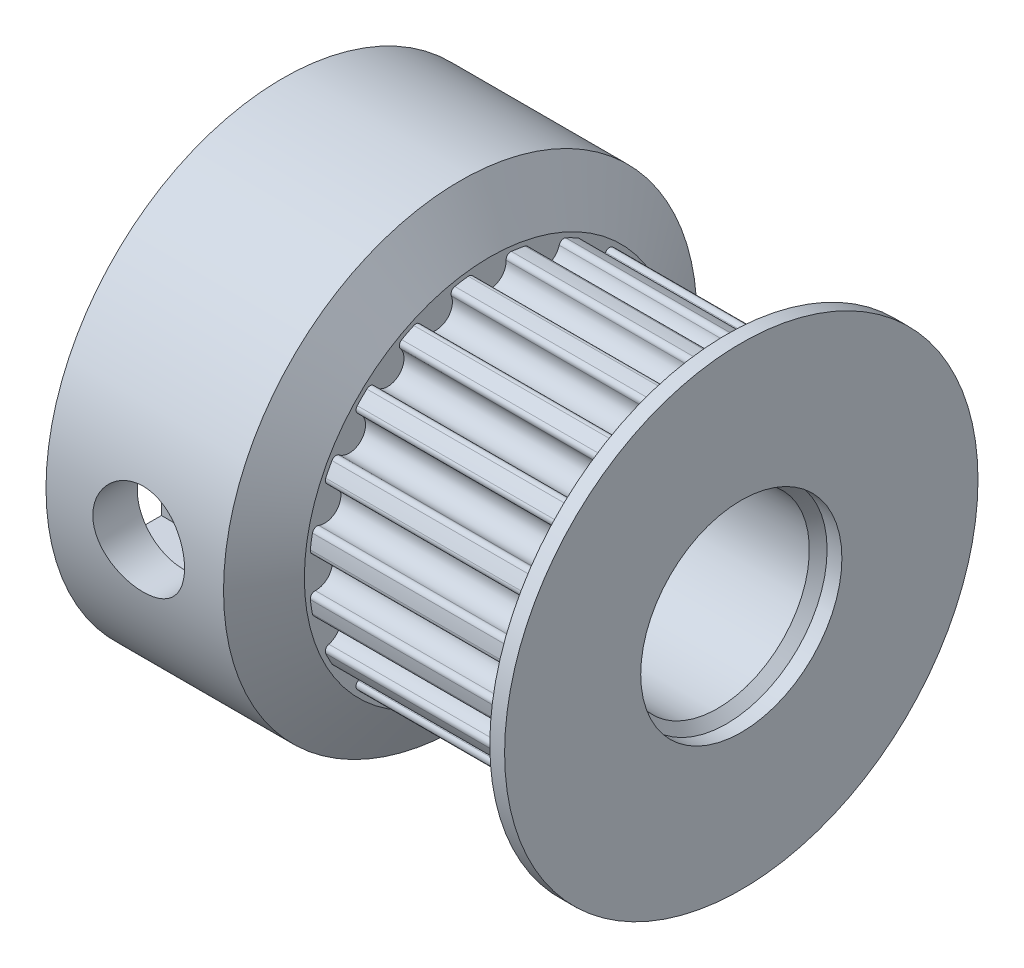
SolidWorks part; units mm, degrees
note: '?' marks a value the reader was unsure of.
other "Main_Body" parameters "D16"=0.5
material "6061-O (SS)"
ref_plane "Сверху" through (0, 0, 0) normal (0, 0, 1) x (1, 0, 0)
ref_plane "Справа" through (0, 0, 0) normal (0, 1, 0) x (1, 0, 0)
ref_plane "Спереди" through (0, 0, 0) normal (1, 0, 0) x (0, 0, -1)
sketch "Эскиз1" plane through (0, 0, 0) normal (0, 0, 1) x (1, 0, 0)
  line L0 (0, 0) -> (0, 7.2132)
  line L1 (0, 7.2132) -> (0, 8)
  line L2 (0, 8) -> (7, 8)
  line L3 (7, 8) -> (7, 7.2132)
  line L4 (7, 6.11) -> (14, 6.11)
  line L5 (14, 6.11) -> (14, 7.2132)
  line L6 (14, 8) -> (15, 8)
  line L7 (15, 0) -> (15, 8)
  line L11 (0, 0) -> (15, 0)
  line L12 (7, 7.2132) -> (7, 6.11)
  line L13 (14, 7.2132) -> (14, 8)
  dimension "D6" = 6.11
  dimension "D7" = 7
  dimension "D8" = 7
  dimension "D10" = 15
  dimension "D11" = 8
revolve "Body" add sketch "Эскиз1" angle 360 about L11
sketch "Эскиз2" plane through (15, 0, 0) normal (1, 0, 0) x (0, 0, -1)
  circle A0 centre (0, 0) radius 3.1
  dimension "D1" = 6.2
extrude "Bore" cut sketch "Эскиз2" against normal through all
sketch "Эскиз3" plane through (7, 0, 0) normal (1, 0, 0) x (0, 0, -1)
  line L0 (0, 0) -> (9.7637, 0) construction
  circle A0 centre (5.5827, -1.8139) radius 0.55
  circle A1 centre (0, 0) radius 6.42 construction
  circle A2 centre (4.7489, -3.4503) radius 0.55
  circle A3 centre (3.4503, -4.7489) radius 0.55
  circle A4 centre (1.8139, -5.5827) radius 0.55
  circle A5 centre (0, -5.87) radius 0.55
  circle A6 centre (5.87, 0) radius 0.55
  circle A7 centre (-1.8139, -5.5827) radius 0.55
  circle A8 centre (-3.4503, -4.7489) radius 0.55
  circle A9 centre (-4.7489, -3.4503) radius 0.55
  circle A10 centre (-5.5827, -1.8139) radius 0.55
  circle A11 centre (-5.87, 0) radius 0.55
  circle A12 centre (-5.5827, 1.8139) radius 0.55
  circle A13 centre (-4.7489, 3.4503) radius 0.55
  circle A14 centre (-3.4503, 4.7489) radius 0.55
  circle A17 centre (-1.8139, 5.5827) radius 0.55
  circle A18 centre (0, 5.87) radius 0.55
  circle A19 centre (1.8139, 5.5827) radius 0.55
  circle A20 centre (3.4503, 4.7489) radius 0.55
  circle A21 centre (4.7489, 3.4503) radius 0.55
  circle A22 centre (5.5827, 1.8139) radius 0.55
  point P45 (0, 0)
  dimension "D1" = 12.84
  dimension "D2" = 20
  dimension "D3" = 1.1
extrude "20T" cut sketch "Эскиз3" along normal blind 7
fillet "Fillet" radius 0.16 40 edges at (10.5, 0.5045, -6.0891) (10.5, -0.5045, -6.0891) (10.5, -1.4019, -5.947) (10.5, -2.3614, -5.6352) (10.5, -3.171, -5.2227) (10.5, -3.9872, -4.6297) (10.5, -4.6297, -3.9872) (10.5, -5.2227, -3.171) (10.5, -5.6352, -2.3614) (10.5, -5.947, -1.4019) (10.5, -6.0891, -0.5045) (10.5, -6.0891, 0.5045) (10.5, -5.947, 1.4019) (10.5, -5.6352, 2.3614) (10.5, -5.2227, 3.171) (10.5, -4.6297, 3.9872) (10.5, -3.9872, 4.6297) (10.5, -3.171, 5.2227) (10.5, -2.3614, 5.6352) (10.5, -1.4019, 5.947) (10.5, -0.5045, 6.0891) (10.5, 0.5045, 6.0891) (10.5, 1.4019, 5.947) (10.5, 2.3614, 5.6352) (10.5, 3.171, 5.2227) (10.5, 3.9872, 4.6297) (10.5, 4.6297, 3.9872) (10.5, 5.2227, 3.171) (10.5, 5.6352, 2.3614) (10.5, 5.947, 1.4019) (10.5, 6.0891, 0.5045) (10.5, 6.0891, -0.5045) (10.5, 5.947, -1.4019) (10.5, 5.6352, -2.3614) (10.5, 5.2227, -3.171) (10.5, 4.6297, -3.9872) (10.5, 3.9872, -4.6297) (10.5, 3.171, -5.2227) (10.5, 2.3614, -5.6352) (10.5, 1.4019, -5.947)
ref_axis "Axis1" through (0, 0, 0) along (1, 0, 0)?
chamfer "Chamfer2" distance 0.3 angle 45 2 edges at (15, 0, -3.1) (0, 0, -3.1)
sketch "Sketch1" plane through (0, 0, 0) normal (-1, 0, 0) x (0, 0, 1)
  line L1 (6.5, 2.75) -> (4.1, 2.75)
  line L2 (6.5, 2.75) -> (6.5, -2.75)
  line L3 (6.5, -2.75) -> (4.1, -2.75)
  line L4 (4.1, 2.75) -> (4.1, -2.75)
  line L5 (2.75, -4.1) -> (-2.75, -4.1)
  line L6 (2.75, -4.1) -> (2.75, -6.5)
  line L7 (2.75, -6.5) -> (-2.75, -6.5)
  line L8 (-2.75, -4.1) -> (-2.75, -6.5)
  circle A2 centre (0, 0) radius 8 construction
  point P4 (8, 0)
  point P5 (0, -8)
  point P8 (0, -6.5)
  point P9 (6.5, 0)
  dimension "D1" = 5.5
  dimension "D2" = 1.5
  dimension "D3" = 2.4
  dimension "D4" = 1.5
extrude "Cut-Extrude1" cut sketch "Sketch1" against normal blind 6.35
sketch "Sketch2" plane through (0, 0, 4.1) normal (0, 0, 1) x (1, 0, 0)
  line L0 (6.35, -2.75) -> (6.35, 2.75) construction
  line L1 (6.25, 0) -> (4.6912, 2.7)
  line L2 (4.6912, 2.7) -> (1.5735, 2.7)
  line L3 (1.5735, 2.7) -> (0.0146, 0)
  line L4 (0.0146, 0) -> (1.5735, -2.7)
  line L5 (1.5735, -2.7) -> (4.6912, -2.7)
  line L6 (4.6912, -2.7) -> (6.25, 0)
  line L7 (6.35, -2.75) -> (0, -2.75) construction
  circle A0 centre (3.1323, 0) radius 2.7 construction
  circle A1 centre (3.1323, 0) radius 1.55
  dimension "D2" = 3.1
  dimension "D4" = 5.4
  dimension "D1" = 0.1
  dimension "D3" = 0.05
extrude "Cut-Extrude2" cut sketch "Sketch2" against normal up to next and the other way through all contours A1
sketch "Sketch3" plane through (0, -4.1, 0) normal (0, -1, 0) x (1, 0, 0)
  line L0 (6.35, -2.75) -> (6.35, 2.75) construction
  line L1 (6.25, 0) -> (4.6912, 2.7)
  line L2 (4.6912, 2.7) -> (1.5735, 2.7)
  line L3 (1.5735, 2.7) -> (0.0146, 0)
  line L4 (0.0146, 0) -> (1.5735, -2.7)
  line L5 (1.5735, -2.7) -> (4.6912, -2.7)
  line L6 (4.6912, -2.7) -> (6.25, 0)
  line L7 (6.35, 2.75) -> (0, 2.75) construction
  circle A0 centre (3.1323, 0) radius 2.7 construction
  circle A1 centre (3.1323, 0) radius 1.55
  dimension "D1" = 5.4
  dimension "D4" = 3.1
  dimension "D2" = 0.1
  dimension "D3" = 0.05
extrude "Cut-Extrude3" cut sketch "Sketch3" against normal up to next and the other way through all contours A1
sketch "Sketch4" plane through (15, 0, 0) normal (1, 0, 0) x (0, 0, -1)
  circle A0 centre (0, 0) radius 8
  circle A1 centre (0, 0) radius 3.4
extrude "Boss-Extrude1" add sketch "Sketch4" along normal blind 0.5
chamfer "Chamfer3" distance 1 angle 60 2 edges at (7, 0, 8) (14, 0, 8) first distance on face at (7, 0, 8) first distance on face at (14, 0, 8)
